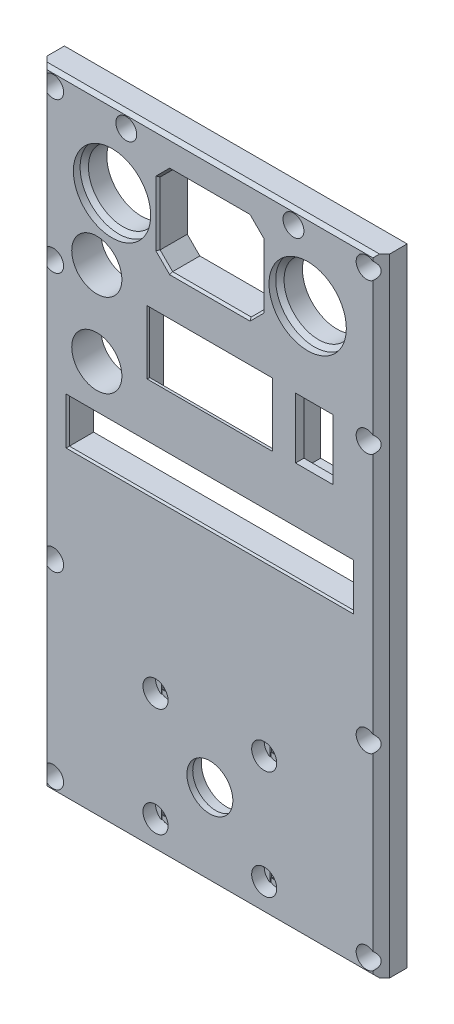
SolidWorks part; units mm, degrees
ref_plane "Front Plane" through (0, 0, 0) normal (0, 0, 1) x (1, 0, 0)
ref_plane "Top Plane" through (0, 0, 0) normal (0, 1, 0) x (1, 0, 0)
ref_plane "Right Plane" through (0, 0, 0) normal (1, 0, 0) x (0, 0, -1)
sketch "Sketch1" plane through (0, 0, 0) normal (0, 0, 1) x (1, 0, 0)
  line L1 (-41, -75) -> (41, -75)
  line L2 (-41, -75) -> (-41, 75)
  line L3 (-41, 75) -> (41, 75)
  line L4 (41, -75) -> (41, 75)
  line L5 (-41, -75) -> (41, 75) construction
  line L6 (-41, 75) -> (41, -75) construction
  line L7 (-34, -68) -> (34, -68)
  line L8 (-34, -68) -> (-34, 68)
  line L9 (-34, 68) -> (34, 68)
  line L10 (34, -68) -> (34, 68)
  line L11 (-34, -68) -> (34, 68) construction
  line L12 (-34, 68) -> (34, -68) construction
  point P0 (0, 0)
  point P6 (0, 0)
  dimension "D1" = 150
  dimension "D2" = 82
  dimension "D3" = 7
  dimension "D4" = 7
extrude "Boss-Extrude1" add sketch "Sketch1" along normal blind 7
sketch "Sketch2" plane through (0, 0, 7) normal (0, 0, 1) x (1, 0, 0)
  line L0 (34, -68) -> (34, 68) construction
  line L1 (-34, -68) -> (34, -68)
  line L2 (-34, -68) -> (-34, -32)
  line L3 (-34, -32) -> (34, -32)
  line L4 (34, -68) -> (34, -32)
  dimension "D1" = 36
extrude "Boss-Extrude2" add sketch "Sketch2" against normal up to surface (7 mm away) up to face at (0, 0, 0)
sketch "Sketch3" plane through (0, 0, 0) normal (0, 0, -1) x (-1, 0, 0)
  line L0 (0, -75) -> (0, -55) construction
  line L1 (41, -75) -> (-41, -75) construction
  circle A0 centre (0, -55) radius 5.5
  dimension "D1" = 11
  dimension "D2" = 20
extrude "Cut-Extrude1" cut sketch "Sketch3" against normal through all
sketch "Sketch4" plane through (0, 0, 0) normal (0, 0, -1) x (-1, 0, 0)
  circle A0 centre (0, -55) radius 6.05
  dimension "D1" = 12.1
extrude "Cut-Extrude2" cut sketch "Sketch4" against normal offset from surface (5.6 mm away) 1.4 up to face at (-5.5, -55, 7)
sketch "Sketch5" plane through (0, 0, 0) normal (0, 0, -1) x (-1, 0, 0)
  circle A0 centre (0, -55) radius 11.1
  dimension "D1" = 22.2
extrude "Cut-Extrude3" cut sketch "Sketch5" against normal offset from surface (3 mm away) 2.6 up to face at (-6.05, -55, 5.6)
sketch "Sketch6" plane through (0, 0, 0) normal (0, 0, -1) x (-1, 0, 0)
  line L1 (-13, -68) -> (13, -68) construction
  line L2 (-13, -68) -> (-13, -42) construction
  line L3 (-13, -42) -> (13, -42) construction
  line L4 (13, -68) -> (13, -42) construction
  line L5 (-13, -68) -> (13, -42) construction
  line L6 (-13, -42) -> (13, -68) construction
  circle A0 centre (-13, -42) radius 1.6
  circle A1 centre (13, -42) radius 1.6
  circle A2 centre (13, -68) radius 1.6
  circle A3 centre (-13, -68) radius 1.6
  point P0 (0, -55)
  dimension "D2" = 3.2
  dimension "D1" = 26
extrude "Cut-Extrude4" cut sketch "Sketch6" against normal through all
sketch "Sketch7" plane through (0, 0, 0) normal (0, 0, -1) x (-1, 0, 0)
  line L1 (-25, -74) -> (25, -74)
  line L2 (-25, -74) -> (-25, -36)
  line L3 (-25, -36) -> (25, -36)
  line L4 (25, -74) -> (25, -36)
  line L5 (-25, -74) -> (25, -36) construction
  line L6 (-25, -36) -> (25, -74) construction
  point P0 (0, -55)
  dimension "D1" = 50
  dimension "D2" = 38
extrude "Cut-Extrude5" cut sketch "Sketch7" against normal blind 1
sketch "Sketch8" plane through (0, 0, 7) normal (0, 0, 1) x (1, 0, 0)
  circle A0 centre (-13, -42) radius 3
  circle A1 centre (13, -42) radius 3
  circle A2 centre (13, -68) radius 3
  circle A3 centre (-13, -68) radius 3
  dimension "D1" = 6
extrude "Cut-Extrude6" cut sketch "Sketch8" against normal blind 3
sketch "Sketch9" plane through (0, 0, 7) normal (0, 0, 1) x (1, 0, 0)
  line L0 (-41, 75) -> (-41, -75) construction
  line L1 (-37.5, -71.5) -> (37.5, -71.5) construction
  line L2 (-37.5, -71.5) -> (-37.5, 71.5) construction
  line L3 (-37.5, 71.5) -> (37.5, 71.5) construction
  line L4 (37.5, -71.5) -> (37.5, 71.5) construction
  line L5 (-37.5, -71.5) -> (37.5, 71.5) construction
  line L6 (-37.5, 71.5) -> (37.5, -71.5) construction
  line L7 (41, 75) -> (-41, 75) construction
  circle A0 centre (-37.5, 71.5) radius 1.35
  circle A1 centre (37.5, 71.5) radius 1.35
  circle A2 centre (37.5, -71.5) radius 1.35
  circle A3 centre (-37.5, -71.5) radius 1.35
  circle A6 centre (-37.5, 35.5) radius 1.35
  circle A7 centre (-37.5, -26.5) radius 1.35
  circle A8 centre (37.5, -26.5) radius 1.35
  circle A9 centre (37.5, 35.5) radius 1.35
  point P0 (0, 0)
  dimension "D3" = 2.7
  dimension "D4" = 45
  dimension "D5" = 36
  dimension "D1" = 3.5
  dimension "D2" = 3.5
extrude "Cut-Extrude7" cut sketch "Sketch9" against normal through all
sketch "Sketch10" plane through (0, 0, 7) normal (0, 0, 1) x (1, 0, 0)
  circle A0 centre (-37.5, 71.5) radius 2.5
  circle A1 centre (37.5, 71.5) radius 2.5
  circle A2 centre (-37.5, 35.5) radius 2.5
  circle A3 centre (-37.5, -26.5) radius 2.5
  circle A4 centre (-37.5, -71.5) radius 2.5
  circle A5 centre (37.5, -71.5) radius 2.5
  circle A6 centre (37.5, 35.5) radius 2.5
  circle A7 centre (37.5, -26.5) radius 2.5
  dimension "D1" = 5
extrude "Cut-Extrude8" cut sketch "Sketch10" against normal blind 5
chamfer "Chamfer1" distance 2 angle 45 2 edges at (-41, 0, 7) (41, 0, 7)
sketch "Sketch11" plane through (0, 0, 7) normal (0, 0, 1) x (1, 0, 0)
  line L0 (34, -32) -> (34, 68) construction
  line L1 (-34, -32) -> (34, -32)
  line L2 (-34, -32) -> (-34, -1.5)
  line L3 (-34, -1.5) -> (34, -1.5)
  line L4 (34, -32) -> (34, -1.5)
  line L5 (-39, -75) -> (39, -75) construction
  dimension "D1" = 73.5
extrude "Boss-Extrude3" add sketch "Sketch11" against normal up to surface (7 mm away) up to face at (38.85, 71.5, 0)
sketch "Sketch12" plane through (0, 0, 2) normal (0, 0, 1) x (1, 0, 0)
  line L2 (-38.85, -73.6042) -> (-38.85, -69.3958)
  line L4 (-36.15, -73.6042) -> (-36.15, -69.3958)
  line L5 (-38.85, -73.6042) -> (-36.15, -69.3958) construction
  line L6 (-38.85, -69.3958) -> (-36.15, -73.6042) construction
  line L8 (-38.85, -28.6042) -> (-38.85, -24.3958)
  line L10 (-36.15, -28.6042) -> (-36.15, -24.3958)
  line L11 (-38.85, -28.6042) -> (-36.15, -24.3958) construction
  line L12 (-38.85, -24.3958) -> (-36.15, -28.6042) construction
  line L14 (-38.85, 33.3958) -> (-38.85, 37.6042)
  line L16 (-36.15, 33.3958) -> (-36.15, 37.6042)
  line L17 (-38.85, 33.3958) -> (-36.15, 37.6042) construction
  line L18 (-38.85, 37.6042) -> (-36.15, 33.3958) construction
  line L20 (-38.85, 69.3958) -> (-38.85, 73.6042)
  line L22 (-36.15, 69.3958) -> (-36.15, 73.6042)
  line L23 (-38.85, 69.3958) -> (-36.15, 73.6042) construction
  line L24 (-38.85, 73.6042) -> (-36.15, 69.3958) construction
  arc A0 (-39, -73.5) -> (-39, -69.5) centre (-37.5, -71.5) ccw construction
  circle A1 centre (-37.5, -26.5) radius 2.5 construction
  circle A2 centre (-37.5, 35.5) radius 2.5 construction
  arc A3 (-39, 69.5) -> (-39, 73.5) centre (-37.5, 71.5) ccw construction
  circle A4 centre (-37.5, 71.5) radius 1.35 construction
  circle A5 centre (-37.5, 71.5) radius 2.5 construction
  arc A6 (-36.15, 73.6042) -> (-38.85, 73.6042) centre (-37.5, 71.5) ccw
  arc A7 (-38.85, 69.3958) -> (-36.15, 69.3958) centre (-37.5, 71.5) ccw
  circle A8 centre (-37.5, 35.5) radius 1.35 construction
  arc A9 (-38.85, 33.3958) -> (-36.15, 33.3958) centre (-37.5, 35.5) ccw
  arc A10 (-36.15, 37.6042) -> (-38.85, 37.6042) centre (-37.5, 35.5) ccw
  circle A11 centre (-37.5, -26.5) radius 1.35 construction
  arc A12 (-38.85, -28.6042) -> (-36.15, -28.6042) centre (-37.5, -26.5) ccw
  arc A13 (-36.15, -24.3958) -> (-38.85, -24.3958) centre (-37.5, -26.5) ccw
  circle A14 centre (-37.5, -71.5) radius 1.35 construction
  arc A16 (-38.85, -73.6042) -> (-36.15, -73.6042) centre (-37.5, -71.5) ccw
  arc A18 (-36.15, -69.3958) -> (-38.85, -69.3958) centre (-37.5, -71.5) ccw
  point P0 (-37.5, -71.5)
  point P9 (-37.5, -26.5)
  point P17 (-37.5, 35.5)
  point P25 (-37.5, 71.5)
extrude "Cut-Extrude9" cut sketch "Sketch12" against normal blind 0.2
sketch "Sketch13" plane through (0, 0, 1.8) normal (0, 0, 1) x (1, 0, 0)
  line L0 (-36.15, -71.5) -> (-36.15, -69.3958) construction
  line L1 (-38.85, -72.85) -> (-36.15, -72.85)
  line L2 (-38.85, -72.85) -> (-38.85, -70.15)
  line L3 (-38.85, -70.15) -> (-36.15, -70.15)
  line L4 (-36.15, -72.85) -> (-36.15, -70.15)
  line L5 (-38.85, -72.85) -> (-36.15, -70.15) construction
  line L6 (-38.85, -70.15) -> (-36.15, -72.85) construction
  line L7 (-36.15, -26.5) -> (-36.15, -24.3958) construction
  line L8 (-38.85, -27.85) -> (-36.15, -27.85)
  line L9 (-38.85, -27.85) -> (-38.85, -25.15)
  line L10 (-38.85, -25.15) -> (-36.15, -25.15)
  line L11 (-36.15, -27.85) -> (-36.15, -25.15)
  line L12 (-38.85, -27.85) -> (-36.15, -25.15) construction
  line L13 (-38.85, -25.15) -> (-36.15, -27.85) construction
  line L14 (-36.15, 33.3958) -> (-36.15, 37.6042) construction
  line L15 (-38.85, 34.15) -> (-36.15, 34.15)
  line L16 (-38.85, 34.15) -> (-38.85, 36.85)
  line L17 (-38.85, 36.85) -> (-36.15, 36.85)
  line L18 (-36.15, 34.15) -> (-36.15, 36.85)
  line L19 (-38.85, 34.15) -> (-36.15, 36.85) construction
  line L20 (-38.85, 36.85) -> (-36.15, 34.15) construction
  line L21 (-36.15, 69.3958) -> (-36.15, 73.6042) construction
  line L22 (-38.85, 70.15) -> (-36.15, 70.15)
  line L23 (-38.85, 70.15) -> (-38.85, 72.85)
  line L24 (-38.85, 72.85) -> (-36.15, 72.85)
  line L25 (-36.15, 70.15) -> (-36.15, 72.85)
  line L26 (-38.85, 70.15) -> (-36.15, 72.85) construction
  line L27 (-38.85, 72.85) -> (-36.15, 70.15) construction
  arc A0 (-36.15, -71.5) -> (-38.85, -71.5) centre (-37.5, -71.5) ccw construction
  arc A1 (-36.15, -26.5) -> (-38.85, -26.5) centre (-37.5, -26.5) ccw construction
  arc A2 (-36.15, 35.5) -> (-38.85, 35.5) centre (-37.5, 35.5) ccw construction
  arc A3 (-36.15, 71.5) -> (-38.85, 71.5) centre (-37.5, 71.5) ccw construction
  point P0 (-37.5, -71.5)
  point P11 (-37.5, -26.5)
  point P22 (-37.5, 35.5)
  point P33 (-37.5, 71.5)
extrude "Cut-Extrude10" cut sketch "Sketch13" against normal blind 0.2
sketch "Sketch14" plane through (0, 0, 4) normal (0, 0, 1) x (1, 0, 0)
  line L2 (-14.6, -44.5377) -> (-14.6, -39.4623)
  line L4 (-11.4, -44.5377) -> (-11.4, -39.4623)
  line L5 (-14.6, -44.5377) -> (-11.4, -39.4623) construction
  line L6 (-14.6, -39.4623) -> (-11.4, -44.5377) construction
  line L8 (-14.6, -70.5377) -> (-14.6, -65.4623)
  line L10 (-11.4, -70.5377) -> (-11.4, -65.4623)
  line L11 (-14.6, -70.5377) -> (-11.4, -65.4623) construction
  line L12 (-14.6, -65.4623) -> (-11.4, -70.5377) construction
  circle A0 centre (-13, -42) radius 3 construction
  circle A1 centre (-13, -68) radius 3 construction
  circle A2 centre (-13, -42) radius 3 construction
  arc A3 (-14.6, -44.5377) -> (-11.4, -44.5377) centre (-13, -42) ccw
  arc A4 (-14.6, -70.5377) -> (-11.4, -70.5377) centre (-13, -68) ccw
  circle A5 centre (-13, -42) radius 1.6 construction
  circle A6 centre (-13, -68) radius 1.6 construction
  arc A7 (-11.4, -39.4623) -> (-14.6, -39.4623) centre (-13, -42) ccw
  arc A8 (-11.4, -65.4623) -> (-14.6, -65.4623) centre (-13, -68) ccw
  point P0 (-13, -42)
  point P8 (-13, -68)
extrude "Cut-Extrude11" cut sketch "Sketch14" against normal blind 0.2
sketch "Sketch15" plane through (0, 0, 3.8) normal (0, 0, 1) x (1, 0, 0)
  line L0 (-11.4, -42) -> (-11.4, -39.4623) construction
  line L1 (-14.6, -43.6) -> (-11.4, -43.6)
  line L2 (-14.6, -43.6) -> (-14.6, -40.4)
  line L3 (-14.6, -40.4) -> (-11.4, -40.4)
  line L4 (-11.4, -43.6) -> (-11.4, -40.4)
  line L5 (-14.6, -43.6) -> (-11.4, -40.4) construction
  line L6 (-14.6, -40.4) -> (-11.4, -43.6) construction
  line L7 (-11.4, -68) -> (-11.4, -65.4623) construction
  line L8 (-14.6, -69.6) -> (-11.4, -69.6)
  line L9 (-14.6, -69.6) -> (-14.6, -66.4)
  line L10 (-14.6, -66.4) -> (-11.4, -66.4)
  line L11 (-11.4, -69.6) -> (-11.4, -66.4)
  line L12 (-14.6, -69.6) -> (-11.4, -66.4) construction
  line L13 (-14.6, -66.4) -> (-11.4, -69.6) construction
  arc A0 (-11.4, -68) -> (-14.6, -68) centre (-13, -68) ccw construction
  arc A1 (-14.6, -42) -> (-11.4, -42) centre (-13, -42) ccw construction
  point P0 (-13, -42)
  point P8 (-13, -68)
extrude "Cut-Extrude12" cut sketch "Sketch15" against normal blind 0.2
mirror "Mirror1" about plane through (0, 0, 0) normal (1, 0, 0) of "Cut-Extrude10", "Cut-Extrude11", "Cut-Extrude12", "Cut-Extrude9"
chamfer "Chamfer2" distance 0.4 angle 45 4 edges at (34, 33.25, 7) (0, 68, 7) (0, -1.5, 7) (-34, 33.25, 7)
chamfer "Chamfer3" distance 0.8 angle 45 4 edges at (-41, 0, 0) (41, 0, 0) (0, -75, 7) (0, 75, 7)
sketch "Sketch16" plane through (0, 0, 0) normal (1, 0, 0) x (0, 0, -1)
  line L0 (0, -4) -> (0, -15.4)
  line L1 (0, 75) -> (0, -75) construction
  line L2 (0, -15.4) -> (3.2, -12.2)
  line L3 (3.2, -12.2) -> (3.2, -7.2)
  line L4 (3.2, -7.2) -> (0, -4)
  line L5 (0, -15.4) -> (0, -19.4) construction
  line L6 (0.6, -7.7) -> (2.6, -7.7)
  line L7 (0.6, -7.7) -> (0.6, -11.7)
  line L8 (0.6, -11.7) -> (2.6, -11.7)
  line L9 (2.6, -7.7) -> (2.6, -11.7)
  line L10 (-1.046, -17.4) -> (12.8392, -17.4) construction
  line L11 (2.6, -27.1) -> (2.6, -23.1)
  line L12 (0.6, -23.1) -> (2.6, -23.1)
  line L13 (0.6, -27.1) -> (0.6, -23.1)
  line L14 (0.6, -27.1) -> (2.6, -27.1)
  line L15 (3.2, -27.6) -> (0, -30.8)
  line L16 (3.2, -22.6) -> (3.2, -27.6)
  line L17 (0, -19.4) -> (3.2, -22.6)
  line L18 (0, -30.8) -> (0, -19.4)
  point P10 (2.6, -9.7)
  point P11 (3.2, -9.7)
  point P24 (0, -17.4)
  dimension "D1" = 5
  dimension "D2" = 2
  dimension "D3" = 0.6
  dimension "D4" = 0.6
  dimension "D5" = 45
  dimension "D6" = 4
  dimension "D7" = 4
  dimension "D8" = 4
extrude "Boss-Extrude4" add sketch "Sketch16" along normal mid plane 2
pattern_linear "LPattern1" count 2 spacing 20 along (1, 0, 0) count 2 spacing 20 along (-1, 0, 0) of "Boss-Extrude4"
sketch "Sketch17" plane through (0, 0, 0) normal (0, 0, -1) x (-1, 0, 0)
  line L0 (-20, 71.5) -> (20, 71.5) construction
  line L1 (-40.2, 75) -> (40.2, 75) construction
  circle A0 centre (-37.5, 71.5) radius 1.35 construction
  circle A1 centre (-37.5, 71.5) radius 1.35 construction
  circle A2 centre (-20, 71.5) radius 1.35
  circle A3 centre (20, 71.5) radius 1.35
  point P3 (0, 71.5)
  point P6 (0, 75)
  dimension "D1" = 40
extrude "Cut-Extrude13" cut sketch "Sketch17" against normal through all
sketch "Sketch18" plane through (0, 0, 7) normal (0, 0, 1) x (1, 0, 0)
  circle A0 centre (-20, 71.5) radius 2.5
  circle A1 centre (20, 71.5) radius 2.5
  arc A2 (-39, 69.5) -> (-39, 73.5) centre (-37.5, 71.5) ccw construction
extrude "Cut-Extrude14" cut sketch "Sketch18" against normal up to surface (5 mm away) up to face at (35.575, 71.5, 2)
sketch "Sketch19" plane through (0, 0, 2) normal (0, 0, 1) x (1, 0, 0)
  line L2 (-21.35, 69.3958) -> (-21.35, 73.6042)
  line L4 (-18.65, 69.3958) -> (-18.65, 73.6042)
  line L5 (-21.35, 69.3958) -> (-18.65, 73.6042) construction
  line L6 (-21.35, 73.6042) -> (-18.65, 69.3958) construction
  line L8 (18.65, 69.3958) -> (18.65, 73.6042)
  line L10 (21.35, 69.3958) -> (21.35, 73.6042)
  line L11 (18.65, 69.3958) -> (21.35, 73.6042) construction
  line L12 (18.65, 73.6042) -> (21.35, 69.3958) construction
  circle A0 centre (-20, 71.5) radius 2.5 construction
  circle A1 centre (20, 71.5) radius 2.5 construction
  circle A2 centre (20, 71.5) radius 1.35 construction
  circle A3 centre (-20, 71.5) radius 1.35 construction
  circle A4 centre (-20, 71.5) radius 2.5 construction
  arc A5 (18.65, 69.3958) -> (21.35, 69.3958) centre (20, 71.5) ccw
  arc A6 (-18.65, 73.6042) -> (-21.35, 73.6042) centre (-20, 71.5) ccw
  arc A7 (21.35, 73.6042) -> (18.65, 73.6042) centre (20, 71.5) ccw
  arc A8 (-21.35, 69.3958) -> (-18.65, 69.3958) centre (-20, 71.5) ccw
  point P0 (-20, 71.5)
  point P8 (20, 71.5)
extrude "Cut-Extrude15" cut sketch "Sketch19" against normal blind 0.2
sketch "Sketch20" plane through (0, 0, 1.8) normal (0, 0, 1) x (1, 0, 0)
  line L0 (-18.65, 69.3958) -> (-18.65, 73.6042) construction
  line L1 (-21.35, 70.15) -> (-18.65, 70.15)
  line L2 (-21.35, 70.15) -> (-21.35, 72.85)
  line L3 (-21.35, 72.85) -> (-18.65, 72.85)
  line L4 (-18.65, 70.15) -> (-18.65, 72.85)
  line L5 (-21.35, 70.15) -> (-18.65, 72.85) construction
  line L6 (-21.35, 72.85) -> (-18.65, 70.15) construction
  line L7 (21.35, 71.5) -> (21.35, 73.6042) construction
  line L8 (18.65, 70.15) -> (21.35, 70.15)
  line L9 (18.65, 70.15) -> (18.65, 72.85)
  line L10 (18.65, 72.85) -> (21.35, 72.85)
  line L11 (21.35, 70.15) -> (21.35, 72.85)
  line L12 (18.65, 70.15) -> (21.35, 72.85) construction
  line L13 (18.65, 72.85) -> (21.35, 70.15) construction
  arc A0 (18.65, 71.5) -> (21.35, 71.5) centre (20, 71.5) ccw construction
  point P0 (-20, 71.5)
  point P8 (20, 71.5)
extrude "Cut-Extrude16" cut sketch "Sketch20" against normal blind 0.2
sketch "Skizze4" plane through (0, 0, 0) normal (0, 0, -1) x (-1, 0, 0)
  line L1 (21, -4) -> (-21, -4)
  line L2 (21, -4) -> (21, -30.8)
  line L3 (21, -30.8) -> (-21, -30.8)
  line L4 (-21, -4) -> (-21, -30.8)
extrude "Schnitt-Linear austragen1" cut sketch "Skizze4" along normal up to surface (3.2 mm away) up to face at (-20, -9.7, -3.2)
sketch "Skizze6" plane through (0, 0, 7) normal (0, 0, 1) x (1, 0, 0)
  line L0 (12.4, 68.4) -> (34.4, 46.4) construction
  line L1 (34.4, 68.4) -> (12.4, 68.4)
  line L2 (34.4, 68.4) -> (34.4, 46.4)
  line L3 (34.4, 46.4) -> (12.4, 46.4)
  line L4 (12.4, 68.4) -> (12.4, 46.4)
  line L5 (23.4, 68.4) -> (23.4, 46.4) construction
  circle A0 centre (23.4, 56.4) radius 8.25
  point P10 (23.4, 57.4)
  dimension "D1" = 16.5
  dimension "D2" = 22
  dimension "D3" = 22
  dimension "D4" = 1
extrude "Aufsatz-Linear austragen1" add sketch "Skizze6" against normal up to surface (7 mm away) up to face at (18.65, 71.5, 0)
sketch "Skizze7" plane through (0, 0, 7) normal (0, 0, 1) x (1, 0, 0)
  circle A0 centre (23.4, 56.4) radius 9.25
  dimension "D1" = 18.5
extrude "Schnitt-Linear austragen2" cut sketch "Skizze7" against normal blind 1.6
chamfer "Fase6" distance 0.5 angle 45 2 edges at (12.4, 57.4, 7) (23.4, 46.4, 7)
chamfer "Fase7" distance 4 angle 45 1 edges at (12.4, 46.4, 3.25)
chamfer "Fase8" distance 1 angle 45 1 edges at (31.65, 56.4, 5.4)
mirror "Mirror2" about plane through (0, 0, 0) normal (1, 0, 0) of "Fase6", "Schnitt-Linear austragen2", "Fase8", "Aufsatz-Linear austragen1", "Fase7"
sketch "Sketch21" plane through (0, 0, 7) normal (0, 0, 1) x (1, 0, 0)
  line L0 (34.4, 46.9) -> (34.4, -1.9) construction
  line L1 (-34.4, 46.9) -> (-15.9, 46.9)
  line L2 (-34.4, 46.9) -> (-34.4, 8.9)
  line L3 (-34.4, 8.9) -> (34.4, 8.9)
  line L4 (34.4, 46.9) -> (34.4, 8.9)
  line L5 (-15.9, 46.9) -> (-12.4, 50.4)
  line L6 (-12.4, 50.4) -> (-12.4, 46.9)
  line L7 (12.4, 50.4) -> (15.9, 46.9)
  line L8 (12.4, 50.4) -> (12.4, 46.9)
  line L9 (-12.4, 46.9) -> (12.4, 46.9)
  line L10 (15.9, 46.9) -> (34.4, 46.9)
  dimension "D1" = 38
extrude "Boss-Extrude5" add sketch "Sketch21" against normal up to surface (7 mm away) up to face at (0, 41.94, 0)
chamfer "Chamfer4" distance 0.5 angle 45 3 edges at (12.4, 48.65, 7) (-12.4, 48.65, 7) (0, 46.9, 7)
sketch "Sketch22" plane through (0, 0, 0) normal (0, 0, -1) x (-1, 0, 0)
  line L0 (0, 53.9653) -> (0, 1.6347) construction
  line L3 (-17.8, 10.95) -> (17.8, 10.95) construction
  line L8 (-17.8, 10.95) -> (-17.8, 44.65) construction
  line L9 (-17.8, 44.65) -> (17.8, 44.65) construction
  line L10 (17.8, 10.95) -> (17.8, 44.65) construction
  line L11 (-17.8, 10.95) -> (17.8, 44.65) construction
  line L12 (-17.8, 44.65) -> (17.8, 10.95) construction
  line L13 (-15.2, 13.55) -> (15.2, 13.55) construction
  line L14 (-15.2, 13.55) -> (-15.2, 42.05) construction
  line L15 (-15.2, 42.05) -> (15.2, 42.05) construction
  line L16 (15.2, 13.55) -> (15.2, 42.05) construction
  line L17 (-15.2, 13.55) -> (15.2, 42.05) construction
  line L18 (-15.2, 42.05) -> (15.2, 13.55) construction
  line L19 (-18.05, 10.7) -> (18.05, 10.7)
  line L20 (-18.05, 10.7) -> (-18.05, 44.9)
  line L21 (-18.05, 44.9) -> (18.05, 44.9)
  line L22 (18.05, 10.7) -> (18.05, 44.9)
  line L23 (-18.05, 10.7) -> (18.05, 44.9) construction
  line L24 (-18.05, 44.9) -> (18.05, 10.7) construction
  line L25 (-15, 22.1) -> (15, 22.1) construction
  line L26 (-15, 22.1) -> (-15, 37.3) construction
  line L27 (-15, 37.3) -> (15, 37.3) construction
  line L28 (15, 22.1) -> (15, 37.3) construction
  line L29 (-15, 22.1) -> (15, 37.3) construction
  line L30 (-15, 37.3) -> (15, 22.1) construction
  line L31 (-12.4, 68) -> (12.4, 68) construction
  line L32 (-12.4, 46.9) -> (12.4, 46.9) construction
  circle A0 centre (-15.2, 42.05) radius 1.5 construction
  circle A1 centre (15.2, 42.05) radius 1.5 construction
  circle A2 centre (15.2, 13.55) radius 1.5 construction
  circle A3 centre (-15.2, 13.55) radius 1.5 construction
  point P2 (0, 27.8)
  point P7 (0, 27.8)
  point P16 (0, 27.8)
  point P21 (0, 29.7)
  point P29 (0, 68)
  dimension "D5" = 3
  dimension "D1" = 35.6
  dimension "D2" = 33.7
  dimension "D3" = 30.4
  dimension "D4" = 28.5
  dimension "D6" = 0.25
  dimension "D7" = 0.25
  dimension "D8" = 15.2
  dimension "D9" = 30
  dimension "D10" = 7.35
  dimension "D11" = 2
chamfer "Chamfer5" distance 0.4 angle 45 1 edges at (0, 8.9, 7)
sketch "Sketch24" plane through (0, 0, 7) normal (0, 0, 1) x (1, 0, 0)
  line L1 (-12.9, 68.4) -> (12.9, 68.4)
  line L2 (-12.9, 68.4) -> (-12.9, 46.4)
  line L3 (-12.9, 46.4) -> (12.9, 46.4)
  line L4 (12.9, 68.4) -> (12.9, 46.4)
  line L5 (-12.4, 68) -> (12.4, 68)
  line L6 (-12.4, 68) -> (-12.4, 46.9)
  line L7 (-12.4, 46.9) -> (12.4, 46.9)
  line L8 (12.4, 68) -> (12.4, 46.9)
extrude "Boss-Extrude6" add sketch "Sketch24" against normal up to vertex (0.5 mm away) up to point (12.4, 46.9, 6.5)
chamfer "Chamfer7" distance 3 angle 45 4 edges at (12.4, 46.9, 3.5) (12.4, 68, 3.5) (-12.4, 68, 3.5) (-12.4, 46.9, 3.5)
chamfer "Chamfer8" distance 0.5 angle 45 8 edges at (-10.9, 48.4, 7) (0, 46.9, 7) (10.9, 48.4, 7) (12.4, 57.45, 7) (10.9, 66.5, 7) (0, 68, 7) (-10.9, 66.5, 7) (-12.4, 57.45, 7)
chamfer "Chamfer9" distance 0.8 angle 45 6 edges at (-34, 3.7, 0) (0, 8.9, 0) (34, 3.7, 0) (0, -1.5, 0) (0, -75, 0) (0, 75, 0)
sketch "Sketch28" plane through (0, 0, 7) normal (0, 0, 1) x (1, 0, 0)
  circle A0 centre (23.4, 56.4) radius 10
  dimension "D1" = 20
extrude "Cut-Extrude17" cut sketch "Sketch22" against normal offset from surface (6.4 mm away) 0.6 up to face at (0, 57.45, 7)
sketch "Sketch29" plane through (0, 0, 6.4) normal (0, 0, -1) x (-1, 0, 0)
  line L0 (0, 44.9) -> (0, 10.7) construction
  line L17 (-18.05, 44.9) -> (-13.2, 44.9)
  line L18 (-18.05, 44.9) -> (-18.05, 40.05)
  line L19 (-18.05, 40.05) -> (-13.2, 40.05)
  line L20 (-13.2, 44.9) -> (-13.2, 40.05)
  line L21 (-18.05, 10.7) -> (-13.2, 10.7)
  line L22 (-18.05, 10.7) -> (-18.05, 15.55)
  line L23 (-18.05, 15.55) -> (-13.2, 15.55)
  line L24 (-13.2, 10.7) -> (-13.2, 15.55)
  line L25 (-18.05, 44.9) -> (18.05, 44.9) construction
  line L26 (-18.05, 10.7) -> (18.05, 10.7) construction
  line L27 (13.2, 10.7) -> (13.2, 15.55)
  line L28 (18.05, 15.55) -> (13.2, 15.55)
  line L29 (18.05, 10.7) -> (18.05, 15.55)
  line L30 (18.05, 10.7) -> (13.2, 10.7)
  line L31 (13.2, 44.9) -> (13.2, 40.05)
  line L32 (18.05, 40.05) -> (13.2, 40.05)
  line L33 (18.05, 44.9) -> (18.05, 40.05)
  line L34 (18.05, 44.9) -> (13.2, 44.9)
  circle A0 centre (-15.2, 42.05) radius 1.5 construction
  circle A1 centre (-15.2, 13.55) radius 1.5 construction
  dimension "D2" = 2
  dimension "D3" = 2
  dimension "D4" = 2
  dimension "D1" = 2
extrude "Boss-Extrude9" add sketch "Sketch29" along normal blind 1.8
sketch "Sketch30" plane through (0, 0, 6.4) normal (0, 0, -1) x (-1, 0, 0)
  line L0 (15, 22.1) -> (15, 37.3) construction
  line L1 (-15, 22.1) -> (15, 22.1) construction
  line L2 (-15, 22.1) -> (-15, 37.3) construction
  line L3 (-15, 37.3) -> (15, 37.3) construction
  line L4 (15, 22.1) -> (15, 37.3)
  line L5 (-15, 22.1) -> (15, 22.1)
  line L6 (-15, 22.1) -> (-15, 37.3)
  line L7 (-15, 37.3) -> (15, 37.3)
extrude "Cut-Extrude18" cut sketch "Sketch30" against normal through all
sketch "Sketch32" plane through (0, 0, 4.6) normal (0, 0, -1) x (-1, 0, 0)
  circle A0 centre (-15.2, 42.05) radius 1.55
  circle A1 centre (15.2, 42.05) radius 1.55
  circle A2 centre (15.2, 13.55) radius 1.55
  circle A3 centre (-15.2, 13.55) radius 1.55
  dimension "D1" = 3.1
extrude "Boss-Extrude10" add sketch "Sketch32" along normal blind 2
sketch "Sketch33" plane through (0, 0, 7) normal (0, 0, 1) x (1, 0, 0)
  line L0 (15, 37.3) -> (15, 22.1) construction
  line L1 (20.5, 22.45) -> (29.5, 22.45)
  line L2 (20.5, 22.45) -> (20.5, 36.95)
  line L3 (20.5, 36.95) -> (29.5, 36.95)
  line L4 (29.5, 22.45) -> (29.5, 36.95)
  line L5 (20.5, 22.45) -> (29.5, 36.95) construction
  line L6 (20.5, 36.95) -> (29.5, 22.45) construction
  point P0 (25, 29.7)
  point P8 (15, 29.7)
  dimension "D1" = 9
  dimension "D2" = 14.5
  dimension "D3" = 10
extrude "Cut-Extrude19" cut sketch "Sketch33" against normal through all
sketch "Sketch34" plane through (0, 0, 0) normal (0, 0, -1) x (-1, 0, 0)
  line L0 (-29.5, 36.95) -> (-20.5, 22.45) construction
  line L1 (-29.5, 22.45) -> (-29.5, 36.95) construction
  line L2 (-30.5, 19.45) -> (-19.5, 19.45)
  line L3 (-30.5, 19.45) -> (-30.5, 39.95)
  line L4 (-30.5, 39.95) -> (-19.5, 39.95)
  line L5 (-19.5, 19.45) -> (-19.5, 39.95)
  line L6 (-30.5, 19.45) -> (-19.5, 39.95) construction
  line L7 (-30.5, 39.95) -> (-19.5, 19.45) construction
  line L8 (-29.5, 36.95) -> (-20.5, 36.95) construction
  point P4 (-25, 29.7)
  dimension "D1" = 1
  dimension "D2" = 3
extrude "Cut-Extrude20" cut sketch "Sketch34" against normal offset from surface (5 mm away) 2 up to face at (25, 29.7, 7)
sketch "Sketch35" plane through (0, 0, 0) normal (0, 0, -1) x (-1, 0, 0)
  line L0 (-19.5, 29.7) -> (27.05, 29.7) construction
  line L1 (-19.5, 19.45) -> (-19.5, 39.95) construction
  line L2 (27.05, 19.7) -> (27.05, 39.7) construction
  line L3 (18.05, 10.7) -> (18.05, 44.9) construction
  circle A0 centre (27.05, 39.7) radius 6
  circle A1 centre (27.05, 19.7) radius 6
  point P7 (27.05, 29.7)
  dimension "D1" = 12
  dimension "D2" = 20
  dimension "D3" = 9
extrude "Cut-Extrude21" cut sketch "Sketch35" against normal through all
sketch "Sketch36" plane through (0, 0, 7) normal (0, 0, 1) x (1, 0, 0)
  circle A0 centre (-27.05, 39.7) radius 7
  circle A1 centre (-27.05, 19.7) radius 7
  dimension "D1" = 14
